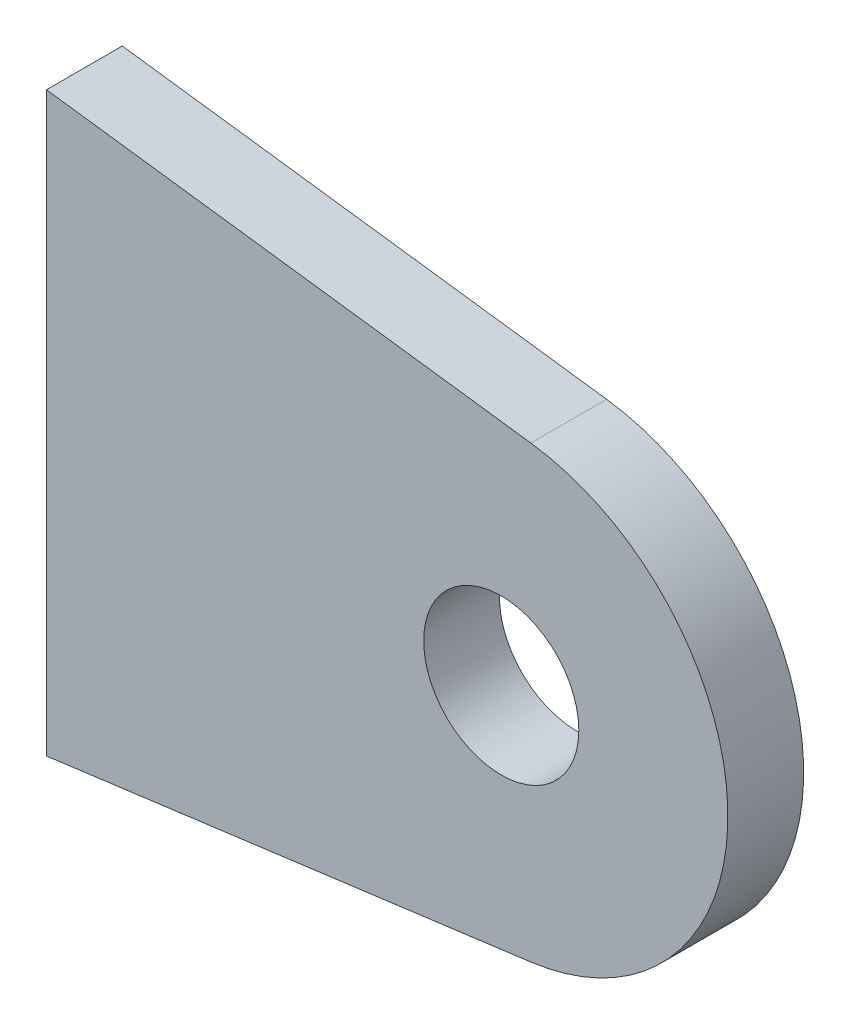
SolidWorks part; units mm, degrees
material "AISI 4130 Steel, annealed at 865C"
ref_plane "X-Y Datum" through (0, 0, 0) normal (0, 0, 1) x (1, 0, 0)
ref_plane "X-Z Datum" through (0, 0, 0) normal (0, 1, 0) x (1, 0, 0)
ref_plane "Y-Z Datum" through (0, 0, 0) normal (1, 0, 0) x (0, 0, -1)
sketch "Sketch1" plane through (-1053.7408, 0, 0) normal (0, 0, 1) x (1, 0, 0)
  line L0 (1054.9803, -9.4147) -> (1034.6908, -12.0859)
  line L1 (1054.9803, 9.4147) -> (1034.6908, 12.0859)
  line L2 (1034.6908, -12.0859) -> (1034.6908, 12.0859)
  circle A0 centre (1053.7408, 0) radius 3.25
  circle A1 centre (1053.7408, 0) radius 9.4959
  circle A4 centre (1053.7408, 0) radius 11.43 construction
  dimension "D3" = 18.9919
  dimension "D4" = 6.5
  dimension "D5" = 22.86
  dimension "D1" = 15
  dimension "D2" = 19.05
extrude "Boss-Extrude1" add sketch "Sketch1" along normal blind 3.175 contours A1 L1 L2 L0 | A1 | A1 | A1 L1 | A0 region at (-12.9527, 0, 0) region at (-9.2273, 0, 0)
